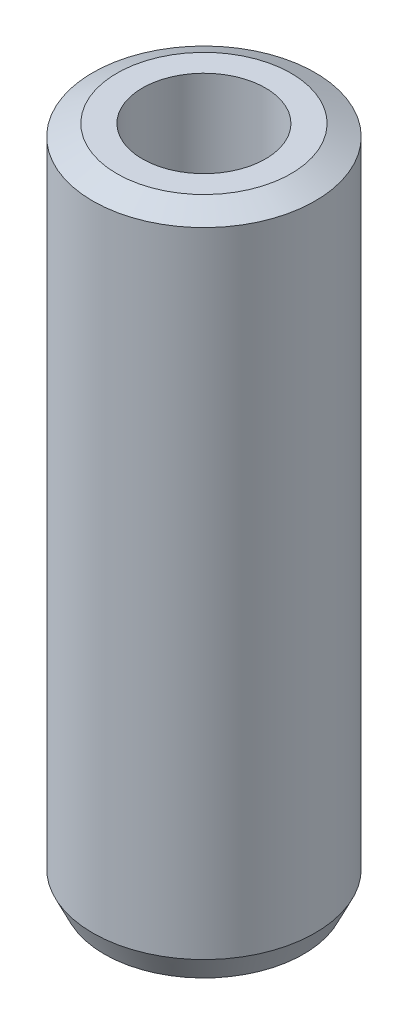
SolidWorks part; units mm, degrees
ref_plane "Front Plane" through (0, 0, 0) normal (0, 0, 1) x (1, 0, 0)
ref_plane "Top Plane" through (0, 0, 0) normal (0, 1, 0) x (1, 0, 0)
ref_plane "Right Plane" through (0, 0, 0) normal (1, 0, 0) x (0, 0, -1)
sketch "Sketch1" plane through (0, 0, 0) normal (0, 1, 0) x (1, 0, 0)
  circle A0 centre (0, 0) radius 50
  dimension "SHAFT_OD" = 100
extrude "Boss-Extrude1" add sketch "Sketch1" along normal blind 301.031
sketch "Sketch2" plane through (0, 0, 0) normal (0, 1, 0) x (1, 0, 0)
  circle A0 centre (0, 0) radius 27.668
  dimension "BORE_D" = 55.336
extrude "Cut-Extrude1" cut sketch "Sketch2" along normal through all
chamfer "Chamfer1" distance 5.199 angle 64.39 2 edges at (0, 301.031, 50) (0, 0, 50) first distance on face at (0, 301.031, 50) first distance on face at (0, 0, 27.668)
